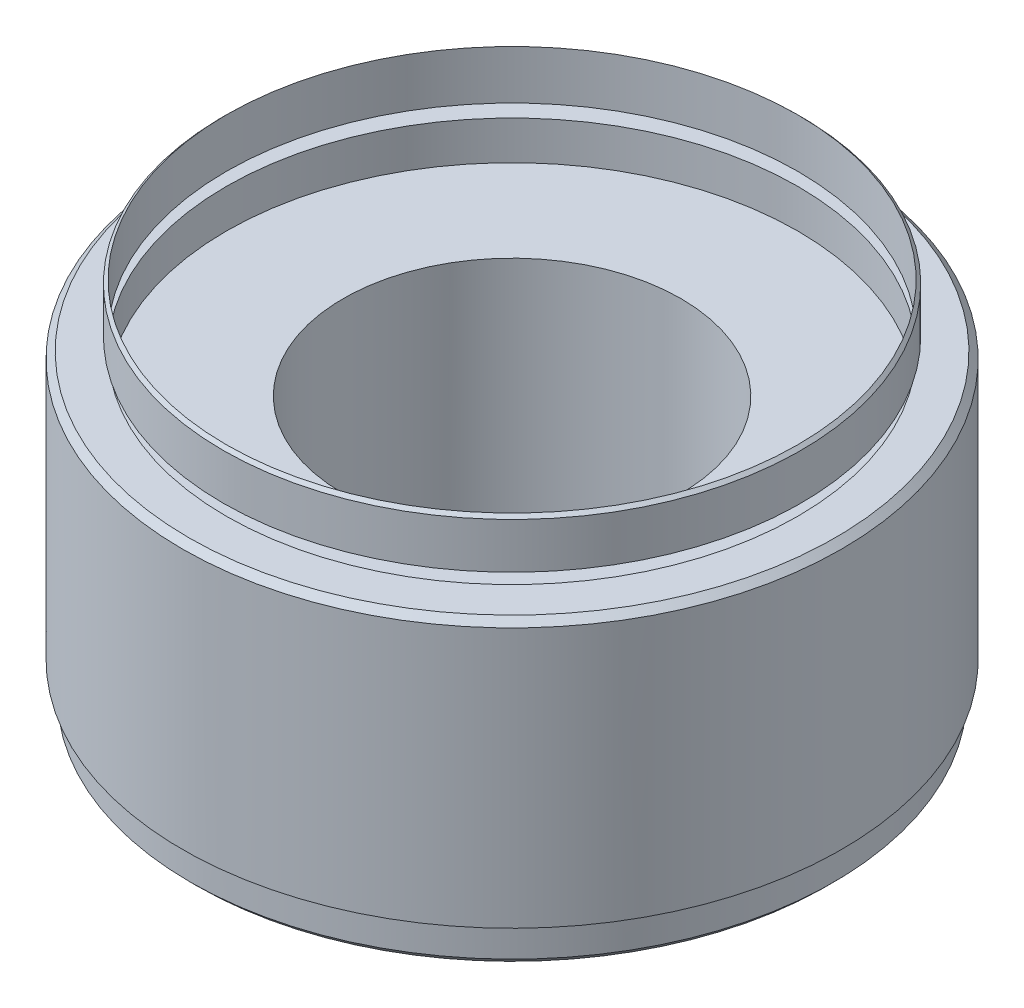
SolidWorks part; units mm, degrees
ref_plane "Front Plane" through (0, 0, 0) normal (0, 0, 1) x (1, 0, 0)
ref_plane "Top Plane" through (0, 0, 0) normal (0, 1, 0) x (1, 0, 0)
ref_plane "Right Plane" through (0, 0, 0) normal (1, 0, 0) x (0, 0, -1)
sketch "Sketch1" plane through (0, 0, 0) normal (0, 1, 0) x (1, 0, 0)
  circle A0 centre (0, 0) radius 25.375
extrude "Main Body" add sketch "Sketch1" along normal blind 28.55 separate body
sketch "Sketch2" plane through (0, 0, 0) normal (0, -1, 0) x (1, 0, 0)
  circle A0 centre (0, 0) radius 24.75
extrude "Bottom Step" cut sketch "Sketch2" against normal blind 3 flip side to cut
sketch "Sketch3" plane through (0, 28.55, 0) normal (0, 1, 0) x (1, 0, 0)
  circle A0 centre (0, 0) radius 22.25
extrude "Top Diameter" cut sketch "Sketch3" against normal blind 5.02 flip side to cut
sketch "Sketch4" plane through (0, 23.53, 0) normal (0, 1, 0) x (1, 0, 0)
  circle A0 centre (0, 0) radius 21.75
extrude "Cut-Extrude3" cut sketch "Sketch4" along normal blind 1 flip side to cut
sketch "Sketch5" plane through (0, 28.55, 0) normal (0, 1, 0) x (1, 0, 0)
  circle A0 centre (0, 0) radius 22
extrude "Insert Bore" cut sketch "Sketch5" against normal blind 8
sketch "Sketch6" plane through (0, 0, 0) normal (0, -1, 0) x (1, 0, 0)
  circle A0 centre (0, 0) radius 13
extrude "Cut-Extrude5" cut sketch "Sketch6" against normal through all
chamfer "Bottom Edge Chamfer" distance 0.5 angle 45 1 edges at (0, 0, -24.75) first distance on face at (0, 0, -13)
chamfer "Top Face Chamfer" distance 0.5 angle 45 1 edges at (0, 28.55, 22.25) first distance on face at (0, 28.55, 22)
chamfer "Body To Top Face Chamfer" distance 0.5 angle 45 1 edges at (0, 23.53, 25.375) first distance on face at (0, 23.53, 22)
